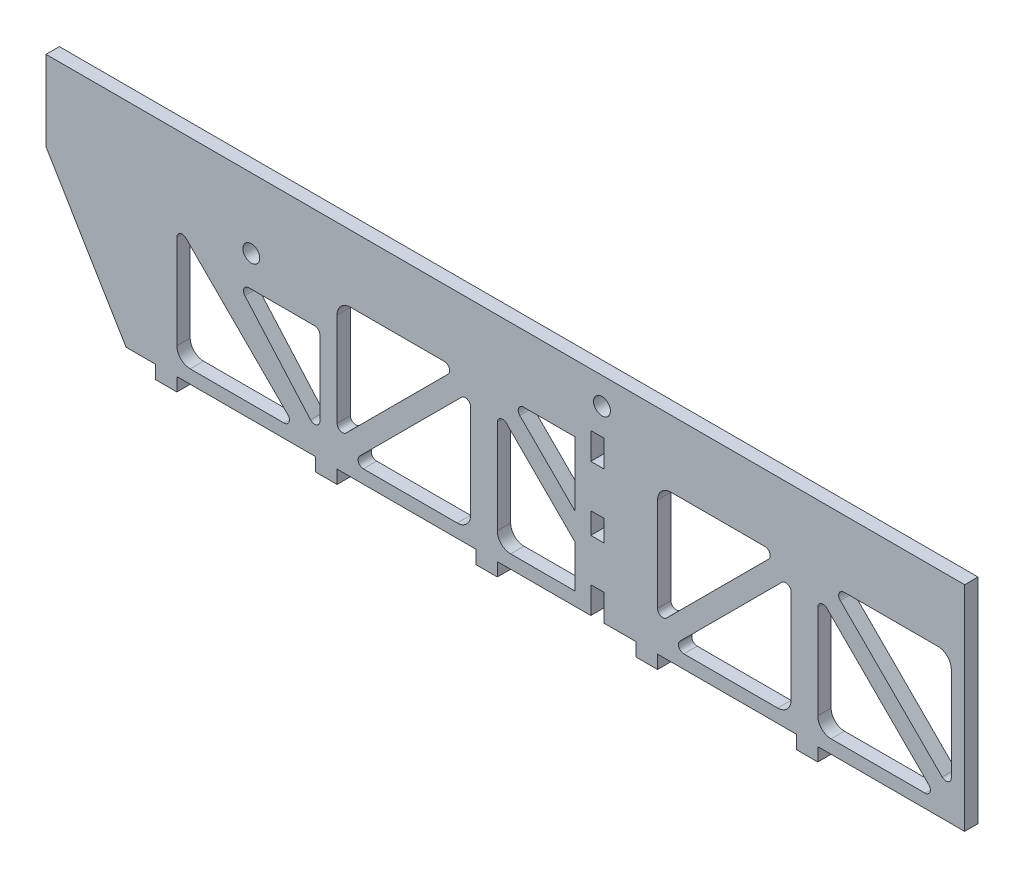
SolidWorks part; units mm, degrees
material "Pine"
ref_plane "Front Plane" through (0, 0, 0) normal (0, 0, 1) x (1, 0, 0)
ref_plane "Top Plane" through (0, 0, 0) normal (0, 1, 0) x (1, 0, 0)
ref_plane "Right Plane" through (0, 0, 0) normal (1, 0, 0) x (0, 0, -1)
sketch "Model" plane through (0, 0, 0) normal (0, 0, 1) x (1, 0, 0)
  line L0 (-306.6281, 15.625) -> (-306.6281, 51.1493)
  line L1 (-309.1681, 53.6893) -> (-340.406, 53.6893)
  line L2 (-342.3135, 49.472) -> (-311.0755, 13.9477)
  line L8 (-171.2321, 6.35) -> (-215.9, 6.35)
  line L9 (-222.25, 57.3679) -> (-222.25, 12.7)
  line L10 (-217.9139, 59.1639) -> (-169.4361, 10.6861)
  line L11 (-234.95, 57.3679) -> (-234.95, 12.7)
  line L12 (-241.3, 6.35) -> (-285.9679, 6.35)
  line L13 (-239.2861, 59.1639) -> (-287.7639, 10.6861)
  line L14 (-294.1139, 17.0361) -> (-245.6361, 65.5139)
  line L15 (-298.45, 63.5) -> (-298.45, 18.8321)
  line L16 (-247.4321, 69.85) -> (-292.1, 69.85)
  line L17 (-323.6321, 6.35) -> (-368.3, 6.35)
  line L18 (-374.65, 57.3679) -> (-374.65, 12.7)
  line L19 (-370.3139, 59.1639) -> (-321.8361, 10.6861)
  line L20 (-18.8321, 6.35) -> (-63.5, 6.35)
  line L21 (-69.85, 57.3679) -> (-69.85, 12.7)
  line L22 (-17.0361, 10.6861) -> (-65.5139, 59.1639)
  line L23 (-82.55, 57.3679) -> (-82.55, 12.7)
  line L24 (-88.9, 6.35) -> (-133.5679, 6.35)
  line L25 (-86.8861, 59.1639) -> (-135.3639, 10.6861)
  line L26 (-93.2361, 65.5139) -> (-141.7139, 17.0361)
  line L27 (-146.05, 63.5) -> (-146.05, 18.8321)
  line L28 (-95.0321, 69.85) -> (-139.7, 69.85)
  line L29 (-163.0861, 17.0361) -> (-211.5639, 65.5139)
  line L30 (-165.1, 69.85) -> (-209.7679, 69.85)
  line L31 (-158.75, 63.5) -> (-158.75, 18.8321)
  line L35 (-398.78, 0) -> (-436.88, 63.5)
  line L36 (0, 0) -> (-398.78, 0)
  line L37 (0, 0) -> (0, 95.25)
  line L38 (0, 95.25) -> (-436.88, 95.25)
  line L39 (-436.88, 63.5) -> (-436.88, 95.25)
  line L40 (-6.35, 63.5) -> (-6.35, 18.8321)
  line L41 (-59.1639, 65.5139) -> (-10.6861, 17.0361)
  line L42 (-12.7, 69.85) -> (-57.3679, 69.85)
  arc A0 (-222.25, 12.7) -> (-215.9, 6.35) centre (-215.9, 12.7) ccw
  arc A1 (-217.9139, 59.1639) -> (-222.25, 57.3679) centre (-219.71, 57.3679) ccw
  arc A2 (-171.2321, 6.35) -> (-169.4361, 10.6861) centre (-171.2321, 8.89) ccw
  arc A3 (-234.95, 57.3679) -> (-239.2861, 59.1639) centre (-237.49, 57.3679) ccw
  arc A4 (-241.3, 6.35) -> (-234.95, 12.7) centre (-241.3, 12.7) ccw
  arc A5 (-287.7639, 10.6861) -> (-285.9679, 6.35) centre (-285.9679, 8.89) ccw
  arc A6 (-245.6361, 65.5139) -> (-247.4321, 69.85) centre (-247.4321, 67.31) ccw
  arc A7 (-298.45, 18.8321) -> (-294.1139, 17.0361) centre (-295.91, 18.8321) ccw
  arc A8 (-292.1, 69.85) -> (-298.45, 63.5) centre (-292.1, 63.5) ccw
  arc A9 (-323.6321, 6.35) -> (-321.8361, 10.6861) centre (-323.6321, 8.89) ccw
  arc A10 (-374.65, 12.7) -> (-368.3, 6.35) centre (-368.3, 12.7) ccw
  arc A11 (-370.3139, 59.1639) -> (-374.65, 57.3679) centre (-372.11, 57.3679) ccw
  arc A12 (-69.85, 12.7) -> (-63.5, 6.35) centre (-63.5, 12.7) ccw
  arc A13 (-65.5139, 59.1639) -> (-69.85, 57.3679) centre (-67.31, 57.3679) ccw
  arc A14 (-18.8321, 6.35) -> (-17.0361, 10.6861) centre (-18.8321, 8.89) ccw
  arc A15 (-82.55, 57.3679) -> (-86.8861, 59.1639) centre (-85.09, 57.3679) ccw
  arc A16 (-88.9, 6.35) -> (-82.55, 12.7) centre (-88.9, 12.7) ccw
  arc A17 (-135.3639, 10.6861) -> (-133.5679, 6.35) centre (-133.5679, 8.89) ccw
  arc A18 (-93.2361, 65.5139) -> (-95.0321, 69.85) centre (-95.0321, 67.31) ccw
  arc A19 (-146.05, 18.8321) -> (-141.7139, 17.0361) centre (-143.51, 18.8321) ccw
  arc A20 (-139.7, 69.85) -> (-146.05, 63.5) centre (-139.7, 63.5) ccw
  arc A21 (-163.0861, 17.0361) -> (-158.75, 18.8321) centre (-161.29, 18.8321) ccw
  arc A22 (-209.7679, 69.85) -> (-211.5639, 65.5139) centre (-209.7679, 67.31) ccw
  arc A23 (-158.75, 63.5) -> (-165.1, 69.85) centre (-165.1, 63.5) ccw
  arc A24 (-306.6281, 15.625) -> (-311.0755, 13.9477) centre (-309.1681, 15.625) cw
  arc A25 (-340.406, 53.6893) -> (-342.3135, 49.472) centre (-340.406, 51.1493) ccw
  arc A26 (-306.6281, 51.1493) -> (-309.1681, 53.6893) centre (-309.1681, 51.1493) ccw
  arc A27 (-10.6861, 17.0361) -> (-6.35, 18.8321) centre (-8.89, 18.8321) ccw
  arc A28 (-57.3679, 69.85) -> (-59.1639, 65.5139) centre (-57.3679, 67.31) ccw
  arc A29 (-6.35, 63.5) -> (-12.7, 69.85) centre (-12.7, 63.5) ccw
  circle A30 centre (-172.466, 88.9) radius 4
  circle A31 centre (-339.2348, 68.4233) radius 4
  dimension "D2" = 172.466
  dimension "D4" = 8
  dimension "D5" = 166.7688
  dimension "D7" = 8
  dimension "D6" = 20.4767
  dimension "D8" = 2.54
  dimension "D1" = 95.25
  dimension "D3" = 6.35
extrude "Boss-Extrude1" add sketch "Model" along normal blind 6.35
sketch "Sketch1" plane through (0, 0, 6.35) normal (0, 0, 1) x (1, 0, 0)
  line L0 (-69.85, 95.25) -> (-69.85, 0) construction
  line L1 (-69.85, 57.3679) -> (-69.85, 12.7) construction
  line L2 (-398.78, 0) -> (0, 0) construction
  line L3 (-146.05, 95.25) -> (-146.05, 0) construction
  line L4 (-146.05, 63.5) -> (-146.05, 18.8321) construction
  line L5 (-222.25, 95.25) -> (-222.25, 0) construction
  line L6 (-222.25, 57.3679) -> (-222.25, 12.7) construction
  line L7 (-298.45, 95.25) -> (-298.45, 0) construction
  line L8 (-298.45, 63.5) -> (-298.45, 18.8321) construction
  line L9 (-374.65, 95.25) -> (-374.65, 0) construction
  line L10 (-374.65, 57.3679) -> (-374.65, 12.7) construction
  line L11 (0, 95.25) -> (-436.88, 95.25) construction
  line L12 (-69.85, 0) -> (-80.01, 0)
  line L13 (-69.85, 0) -> (-69.85, -6.35)
  line L14 (-69.85, -6.35) -> (-80.01, -6.35)
  line L15 (-80.01, 0) -> (-80.01, -6.35)
  line L16 (-146.05, 0) -> (-156.21, 0)
  line L17 (-146.05, 0) -> (-146.05, -6.35)
  line L18 (-146.05, -6.35) -> (-156.21, -6.35)
  line L19 (-156.21, 0) -> (-156.21, -6.35)
  line L20 (-222.25, 0) -> (-232.41, 0)
  line L21 (-222.25, 0) -> (-222.25, -6.35)
  line L22 (-222.25, -6.35) -> (-232.41, -6.35)
  line L23 (-232.41, 0) -> (-232.41, -6.35)
  line L24 (-298.45, 0) -> (-308.61, 0)
  line L25 (-298.45, 0) -> (-298.45, -6.35)
  line L26 (-298.45, -6.35) -> (-308.61, -6.35)
  line L27 (-308.61, 0) -> (-308.61, -6.35)
  line L28 (-374.65, 0) -> (-384.81, 0)
  line L29 (-374.65, 0) -> (-374.65, -6.35)
  line L30 (-374.65, -6.35) -> (-384.81, -6.35)
  line L31 (-384.81, 0) -> (-384.81, -6.35)
  line L32 (0, 0) -> (0, 95.25) construction
  line L53 (-436.88, 95.25) -> (0, 95.25)
  line L54 (-436.88, 95.25) -> (-436.88, 101.6)
  line L55 (-436.88, 101.6) -> (0, 101.6)
  line L56 (0, 95.25) -> (0, 101.6)
  dimension "D1" = 6.35
  dimension "D2" = 10.16
  dimension "D3" = 10.16
  dimension "D4" = 10.16
  dimension "D5" = 10.16
  dimension "D6" = 10.16
  dimension "D8" = 6.35
extrude "Boss-Extrude2" add sketch "Sketch1" against normal up to surface (6.35 mm away) up to face at (-168.466, 88.9, 0)
sketch "Sketch2" plane through (0, 0, 0) normal (0, 0, -1) x (-1, 0, 0)
  line L0 (158.75, 18.8321) -> (158.75, 63.5) construction
  line L1 (185.42, 69.85) -> (165.1, 69.85)
  line L2 (185.42, 69.85) -> (185.42, 0)
  line L3 (185.42, 0) -> (165.1, 0)
  line L4 (165.1, 69.85) -> (165.1, 0)
  line L6 (222.25, 0) -> (156.21, 0) construction
  line L8 (165.1, 69.85) -> (209.7679, 69.85) construction
  line L10 (156.21, -6.35) -> (146.05, -6.35) construction
  line L11 (177.8, 0) -> (171.45, 0)
  line L12 (177.8, 0) -> (177.8, 12.7)
  line L13 (177.8, 12.7) -> (171.45, 12.7)
  line L14 (171.45, 0) -> (171.45, 12.7)
  line L15 (177.8, 33.02) -> (171.45, 33.02)
  line L16 (177.8, 33.02) -> (177.8, 43.18)
  line L17 (177.8, 43.18) -> (171.45, 43.18)
  line L18 (171.45, 33.02) -> (171.45, 43.18)
  line L19 (177.8, 63.5) -> (171.45, 63.5)
  line L20 (177.8, 63.5) -> (177.8, 76.2)
  line L21 (177.8, 76.2) -> (171.45, 76.2)
  line L22 (171.45, 63.5) -> (171.45, 76.2)
  dimension "D1" = 6.35
  dimension "D2" = 20.32
  dimension "D3" = 10.16
  dimension "D4" = 12.7
  dimension "D5" = 6.35
  dimension "D6" = 20.32
  dimension "D7" = 20.32
  dimension "D8" = 12.7
  dimension "D9" = 6.35
  dimension "D10" = 6.35
extrude "Boss-Extrude3" add sketch "Sketch2" against normal up to surface (6.35 mm away) contours L4 | L19 L22 L1 L4 L3 L14 L13 L12 L2 L20 L15 L18 L17 L16 region at (-184.6925, 34.925, 0) up to face at (-319.4123, 39.5294, 6.35)
extrude "Cut-Extrude1" cut sketch "Sketch2<3>" against normal blind 6.35 contours L22 L1 L20 L21 | L14 L3 L12 L13 region at (-174.625, 73.025, 0) region at (-174.625, 6.35, 0)
sketch "Sketch2<3>" plane through (0, 0, 0) normal (0, 0, -1) x (-1, 0, 0) same geometry as "Sketch2"
sketch "Sketch3" plane through (0, 0, 0) normal (0, 0, -1) x (-1, 0, 0)
  line L1 (154.4024, 72.7027) -> (167.3891, 72.7027)
  line L2 (154.4024, 72.7027) -> (154.4024, 13.591)
  line L3 (154.4024, 13.591) -> (167.3891, 13.591)
  line L4 (167.3891, 72.7027) -> (167.3891, 13.591)
extrude "Boss-Extrude4" add sketch "Sketch3" against normal up to surface (6.35 mm away) up to face at (-224.7462, 7.8828, 6.35)
equation "\"thick\"=0.25"
equation "\"D1@Boss-Extrude1\"=\"thick\""
